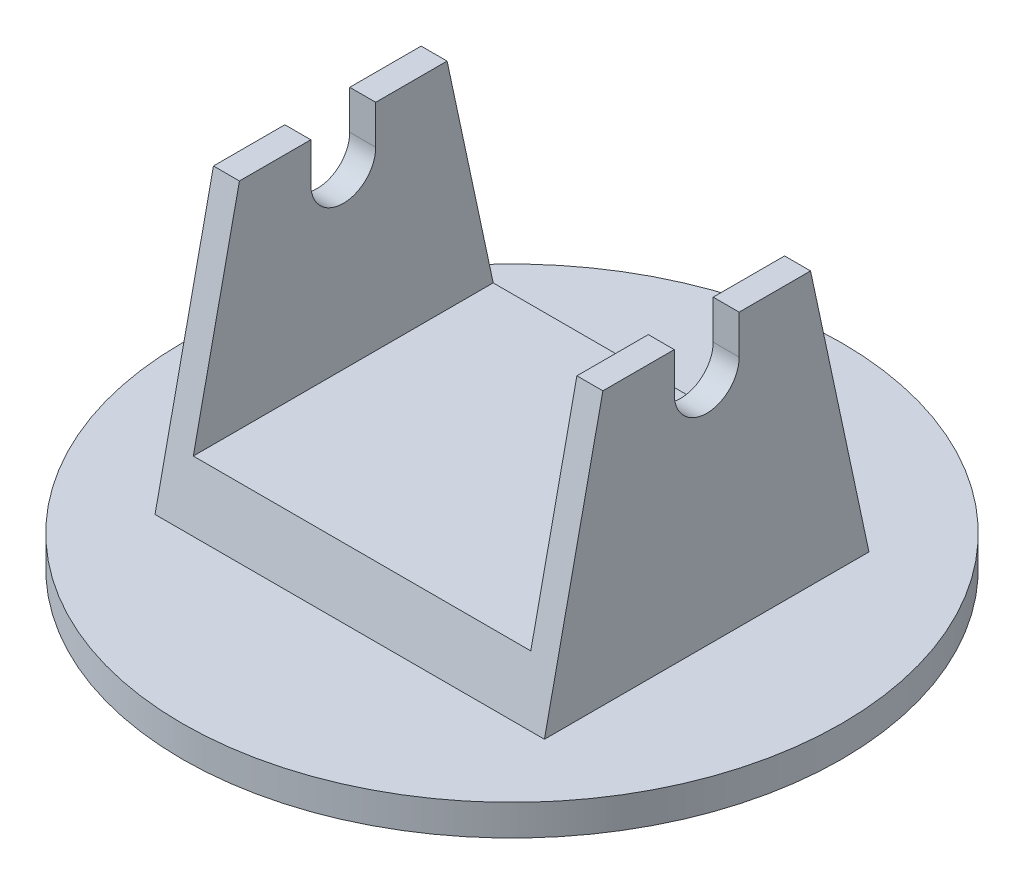
SolidWorks part; units mm, degrees
ref_plane "Front Plane" through (0, 0, 0) normal (0, 0, 1) x (1, 0, 0)
ref_plane "Top Plane" through (0, 0, 0) normal (0, 1, 0) x (1, 0, 0)
ref_plane "Right Plane" through (0, 0, 0) normal (1, 0, 0) x (0, 0, -1)
ref_plane "Plane1" through (0, 0, 0) normal (0, 1, 0) x (-1, 0, 0)
sketch "Sketch2" plane through (0, 0, 0) normal (0, 1, 0) x (-1, 0, 0)
  circle A0 centre (0, 0) radius 50.8
  dimension "D1" = 101.6
extrude "Boss-Extrude1" add sketch "Sketch2" along normal blind 4.7625
sketch "Sketch4" plane through (0, 0, 0) normal (1, 0, 0) x (0, 0, -1)
  line L0 (-25, 4.7625) -> (25, 4.7625)
  line L1 (50.8, 4.7625) -> (-50.8, 4.7625) construction
  line L2 (25, 4.7625) -> (16, 46.7625)
  line L3 (16, 46.7625) -> (-16, 46.7625)
  line L4 (-16, 46.7625) -> (-25, 4.7625)
  line L5 (0, 4.7625) -> (0, 0) construction
  line L6 (0, 4.7625) -> (0, 46.7625) construction
  dimension "D1" = 50
  dimension "D2" = 32
  dimension "D3" = 42
extrude "Boss-Extrude2" add sketch "Sketch4" along normal mid plane 60
sketch "Sketch6" plane through (30, 0, 0) normal (1, 0, 0) x (0, 0, -1)
  line L0 (5, 40.7625) -> (5, 46.7625)
  line L1 (16, 46.7625) -> (-16, 46.7625) construction
  line L2 (-5, 40.7625) -> (-5, 46.7625)
  line L3 (-25, 4.7625) -> (25, 4.7625) construction
  line L4 (-5, 46.7625) -> (5, 46.7625)
  arc A0 (-5, 40.7625) -> (5, 40.7625) centre (0, 40.7625) ccw
  dimension "D1" = 10
  dimension "D2" = 36
extrude "Cut-Extrude2" cut sketch "Sketch6" against normal through all
sketch "Sketch5" plane through (0, 0, 0) normal (0, 0, 1) x (1, 0, 0)
  line L0 (30, 46.7625) -> (-30, 46.7625) construction
  line L1 (-26, 13.6088) -> (26, 13.6088)
  line L2 (-26, 13.6088) -> (-26, 46.7625)
  line L3 (-26, 46.7625) -> (26, 46.7625)
  line L4 (26, 13.6088) -> (26, 46.7625)
  line L5 (-26, 13.6088) -> (26, 46.7625) construction
  line L6 (-26, 46.7625) -> (26, 13.6088) construction
  line L7 (30, 46.7625) -> (30, 4.7625) construction
  line L8 (30, 4.7625) -> (-30, 4.7625) construction
  point P0 (0, 30.1856)
  dimension "D1" = 4
  dimension "D2" = 8.8463
extrude "Cut-Extrude1" cut sketch "Sketch5" against normal through all and the other way through all
